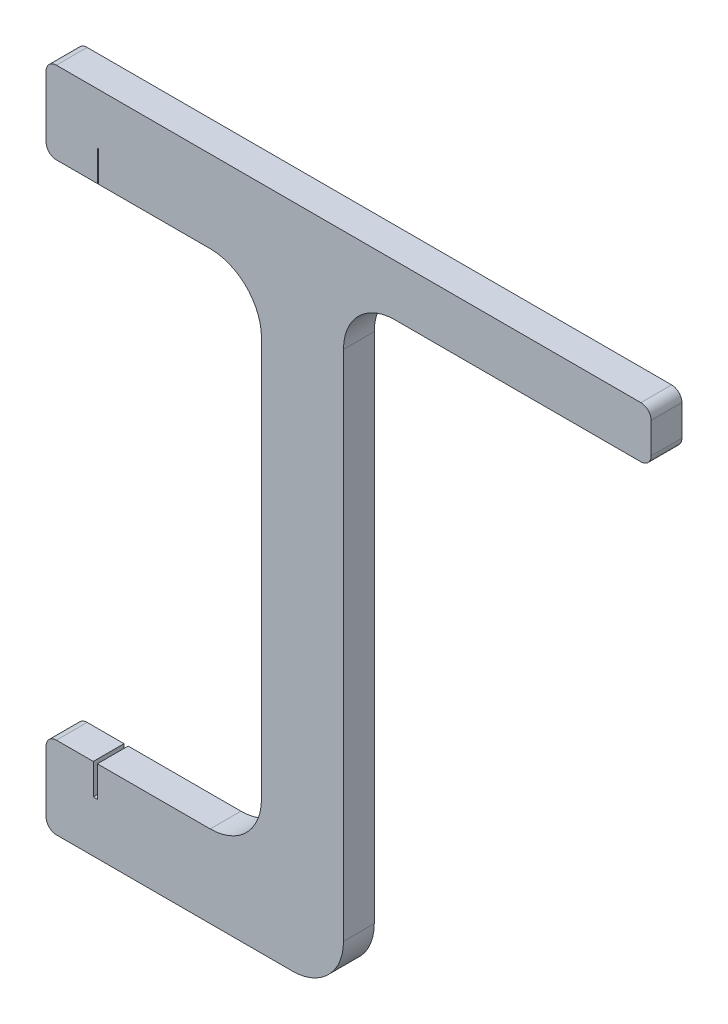
SolidWorks part; units mm, degrees
ref_plane "Front Plane" through (0, 0, 0) normal (0, 0, 1) x (1, 0, 0)
ref_plane "Top Plane" through (0, 0, 0) normal (0, 1, 0) x (1, 0, 0)
ref_plane "Right Plane" through (0, 0, 0) normal (1, 0, 0) x (0, 0, -1)
sketch "Sketch1" plane through (0, 0, 0) normal (0, 0, 1) x (1, 0, 0)
  line L0 (1, 0) -> (24, 0)
  line L1 (29, -10) -> (29, -60)
  line L2 (24, -65) -> (1, -65)
  line L3 (0, -64) -> (0, -58)
  line L4 (1, -57) -> (16, -57)
  line L5 (21, -52) -> (21, -13)
  line L6 (16, -8) -> (1, -8)
  line L7 (0, -7) -> (0, -1)
  line L8 (24, 0) -> (29, 0)
  line L10 (29, 0) -> (58, 0)
  line L11 (59, -1) -> (59, -4)
  line L12 (58, -5) -> (34, -5)
  arc A1 (29, -60) -> (24, -65) centre (24, -60) cw
  arc A2 (21, -13) -> (16, -8) centre (16, -13) ccw
  arc A3 (21, -52) -> (16, -57) centre (16, -52) cw
  arc A4 (0, -1) -> (1, 0) centre (1, -1) cw
  arc A5 (0, -7) -> (1, -8) centre (1, -7) ccw
  arc A6 (1, -65) -> (0, -64) centre (1, -64) cw
  arc A7 (1, -57) -> (0, -58) centre (1, -58) ccw
  arc A8 (34, -5) -> (29, -10) centre (34, -10) ccw
  arc A9 (59, -4) -> (58, -5) centre (58, -4) cw
  arc A10 (59, -1) -> (58, 0) centre (58, -1) ccw
  point P19 (0, 0)
  point P32 (59, -5)
  point P35 (59, 0)
  dimension "D7" = 1
  dimension "D6" = 5
  dimension "D10" = 5
  dimension "D11" = 1
  dimension "D1" = 8
  dimension "D2" = 8
  dimension "D3" = 8
  dimension "D4" = 21
  dimension "D5" = 65
  dimension "D8" = 5
  dimension "D9" = 30
extrude "Boss-Extrude1" add sketch "Sketch1" along normal blind 3
sketch "Sketch2" plane through (0, -57, 0) normal (0, 1, 0) x (1, 0, 0)
  line L0 (29, -1.5) -> (4.8, -1.5) construction
  line L1 (29, -3) -> (29, 0) construction
  line L2 (58, 0) -> (1, 0) construction
  line L3 (4.6, -3) -> (5, -3)
  line L4 (4.6, -3) -> (4.6, 0)
  line L5 (4.6, 0) -> (5, 0)
  line L6 (5, -3) -> (5, 0)
  line L7 (4.6, -3) -> (5, 0) construction
  line L8 (4.6, 0) -> (5, -3) construction
  dimension "D1" = 24.2
  dimension "D2" = 0.4
extrude "Cut-Extrude5" cut sketch "Sketch2" against normal blind 3
sketch "Sketch3" plane through (0, -8, 0) normal (0, -1, 0) x (1, 0, 0)
  line L0 (29, 1.5) -> (5.05, 1.5) construction
  line L1 (29, 3) -> (29, 0) construction
  line L2 (1, 3) -> (16, 3) construction
  line L3 (5, 0) -> (5.1, 0)
  line L4 (5, 0) -> (5, 3)
  line L5 (5, 3) -> (5.1, 3)
  line L6 (5.1, 0) -> (5.1, 3)
  line L7 (5, 0) -> (5.1, 3) construction
  line L8 (5, 3) -> (5.1, 0) construction
  dimension "D1" = 23.95
  dimension "D2" = 0.1
extrude "Cut-Extrude6" cut sketch "Sketch3" against normal blind 3
equation "\"A.L\"= 0.07m"
equation "\"A.h\"= 0.007m"
equation "\"A.d\"= 0.003m"
equation "\"A.delta\"= 45.0001"
equation "\"A.w\"= 0.02m"
equation "\"A.v\"= 0.03m"
equation "\"A.s\"= 0.014m"
equation "\"A.t\"= 0.007m"
equation "\"B.L\"= 0.065m"
equation "\"B.h\"= 0.008m"
equation "\"B.s\"= 0.016m"
equation "\"B.t\"= 0.008m"
equation "\"C.h\"= 0.0065m"
equation "\"C.d\"= 0.003m"
equation "\"C.L\"= 0.05m"
equation "\"C.wmax\"= 0.005m"
equation "\"D.L\"= 0.06m"
equation "\"D.h\"= 0.008m"
equation "\"D.s\"= 0.012m"
equation "\"D.t\"= 0.008m"
equation "\"a_h\"= 0.0002m"
equation "\"a_d\"= 0.003m"
equation "\"a_L\"= 0.008m"
equation "\"b_h\"= 0.0004m"
equation "\"b_d\"= 0.003m"
equation "\"b_L\"= 0.007m"
equation "\"c_h\"= 0.0001m"
equation "\"c_d\"= 0.003m"
equation "\"c_L\"= 0.01m"
equation "\"d_h\"= 0.0001m"
equation "\"d_d\"= 0.003m"
equation "\"d_L\"= 0.01m"
equation "\"S.h\"= 0.015m"
equation "\"S.L\"= 0.09075m"
equation "\"D1@Sketch1\"=\"B.h\""
equation "\"D2@Sketch1\"=\"B.t\""
equation "\"D3@Sketch1\"=\"B.t\""
equation "\"D4@Sketch1\"=\"B.s\"+5"
equation "\"D5@Sketch1\"=\"B.L\""
equation "\"D1@Boss-Extrude1\"=\"A.d\""
equation "\"D1@Sketch2\"=\"B.h\"+\"B.s\"+\"b_h\"/2"
equation "\"D2@Sketch2\"=\"b_h\""
equation "\"D1@Sketch3\"=\"B.h\"+\"B.s\"-\"c_h\"/2"
equation "\"D2@Sketch3\"=\"c_h\""
equation "\"D9@Sketch1\"=\"A.w\"*1.5"
